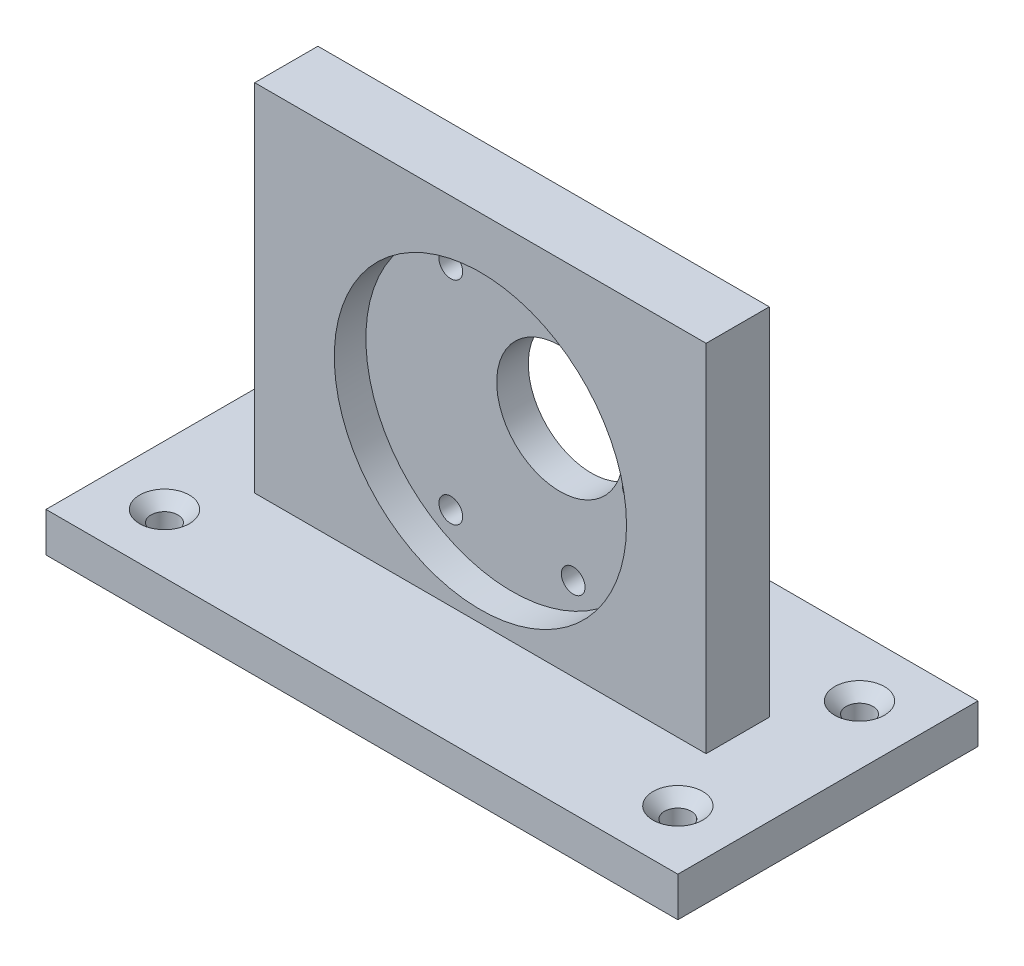
SolidWorks part; units mm, degrees
note: The reader was unsure of these and kept them because the rebuilt part matched: shared geometry of "Sketch3<3>", "Sketch13<2>".
other "Markup1"
sketch "Sketch5" plane through (25, 50, 8) normal (0.9645, 0.1424, 0.2224) x (0.1697, 0.3107, -0.9352)
ref_plane "Front Plane" through (0, 0, 0) normal (0, 0, 1) x (1, 0, 0)
ref_plane "Top Plane" through (0, 0, 0) normal (0, 1, 0) x (1, 0, 0)
ref_plane "Right Plane" through (0, 0, 0) normal (1, 0, 0) x (0, 0, -1)
sketch "Sketch3" plane through (0, 0, 0) normal (0, 0, 1) x (1, 0, 0)
  line L1 (-28.575, 50) -> (28.575, 50)
  line L2 (-28.575, 50) -> (-28.575, 0)
  line L3 (-28.575, 0) -> (28.575, 0)
  line L4 (28.575, 50) -> (28.575, 0)
  line L5 (-7.75, 38.4234) -> (7.75, 38.4234) construction
  line L6 (7.75, 38.4234) -> (15.5, 25) construction
  line L7 (15.5, 25) -> (7.75, 11.5766) construction
  line L8 (7.75, 11.5766) -> (-7.75, 11.5766) construction
  line L9 (-7.75, 11.5766) -> (-15.5, 25) construction
  line L10 (-15.5, 25) -> (-7.75, 38.4234) construction
  line L12 (-20.1843, 13.3466) -> (22.8058, 38.167) construction
  circle A5 centre (-7.75, 38.4234) radius 1.5
  circle A6 centre (7.75, 38.4234) radius 1.5
  circle A8 centre (-7.75, 11.5766) radius 1.5
  circle A9 centre (7.75, 11.5766) radius 1.5
  circle A10 centre (15.5, 25) radius 1.5
  circle A11 centre (6.0622, 28.5) radius 8
  point P4 (0, 0)
  point P27 (-11.625, 18.2883)
  point P28 (11.625, 31.7117)
  dimension "D4" = 25
  dimension "D9" = 16
  dimension "D3" = 3
  dimension "D1" = 50
  dimension "D2" = 57.15
  dimension "D6" = 120
  dimension "D7" = 120
  dimension "D8" = 15.5
  dimension "D10" = 6.4234
extrude "Boss-Extrude1" add sketch "Sketch3" along normal blind 8 contours L2 L3 L4 L1
extrude "Cut-Extrude2" cut sketch "Sketch3<3>" along normal blind 10
sketch "Sketch3<3>" plane through (0, 0, 0) normal (0, 0, 1) x (1, 0, 0) same geometry as "Sketch3"
sketch "Sketch4" plane through (0, 0, 8) normal (0, 0, 1) x (1, 0, 0)
  line L0 (-15.5, 25) -> (15.5, 25) construction
  circle A0 centre (0, 25) radius 18.5
  dimension "D1" = 37
extrude "Cut-Extrude3" cut sketch "Sketch4" against normal blind 4 contours A0
sketch "Sketch6" plane through (0, 0, 8) normal (0, 0, 1) x (1, 0, 0)
  line L1 (-40, 5) -> (40, 5)
  line L2 (-40, 5) -> (-40, 0)
  line L3 (-40, 0) -> (40, 0)
  line L4 (40, 5) -> (40, 0)
  point P4 (0, 0)
  dimension "D1" = 80
  dimension "D2" = 5
extrude "Boss-Extrude2" add sketch "Sketch6" against normal blind 23 and the other way blind 15
sketch "Sketch7" plane through (0, 5, 0) normal (0, 1, 0) x (1, 0, 0)
  line L0 (-40, -23) -> (-40, 15) construction
  line L1 (-40, -23) -> (-32.5, -23)
  line L2 (-40, -23) -> (-40, -15.5)
  line L3 (-40, -15.5) -> (-32.5, -15.5)
  line L4 (-32.5, -23) -> (-32.5, -15.5)
  line L5 (-40, -4) -> (40, -4) construction
  line L6 (40, -23) -> (40, 15) construction
  line L7 (0, 15) -> (0, -23) construction
  line L8 (40, 15) -> (-40, 15) construction
  line L9 (40, -23) -> (-40, -23) construction
  point P18 (-32.5, 7.5)
  point P20 (32.5, -15.5)
  point P21 (32.5, 7.5)
  dimension "D1" = 7.5
hole_wizard "CSK for M3 Flat Head Machine Screw1" positions "Sketch8" profile "Sketch9" countersink size "M3" standard "ANSI Metric" end condition through all
sketch "Sketch8" plane through (0, 5, 0) normal (0, 1, 0) x (1, 0, 0)
  point P0 (-32.5, 7.5)
  point P3 (-32.5, -15.5)
  point P6 (32.5, -15.5)
  point P9 (32.5, 7.5)
sketch "Sketch9" plane through (-32.5, 5, -7.5) normal (1, 0, 0) x (0, 0, 1)
  line L0 (0, 0) -> (0, 5)
  line L1 (0, 5) -> (1.7, 5)
  line L2 (1.7, 5) -> (1.7, 1.45)
  line L3 (1.7, 1.45) -> (3.15, 0)
  line L5 (3.15, 0) -> (0, 0)
  line L6 (-1.7, 1.45) -> (-3.15, 0) construction
  line L11 (0, -6.35) -> (0, 107.95) construction
  dimension "Thru Hole Dia." = 3.4
  dimension "Thru Hole Depth" = 5
  dimension "Near C'Sink Dia." = 6.3
  dimension "Near C'Sink Angle" = 90
sketch "Sketch13" plane through (0, 0, 0) normal (0, 0, -1) x (-1, 0, 0)
  line L0 (20.3378, 28.5) -> (-6.0622, 28.5) construction
  circle A5 centre (20.3378, 28.5) radius 5.08
  circle A7 centre (20.3378, 28.5) radius 6.985
  dimension "D1" = 10.16
  dimension "D2" = 1.905
  dimension "D3" = 26.4
extrude "Boss-Extrude4" add sketch "Sketch13" along normal blind 2.54
extrude "Cut-Extrude6" cut sketch "Sketch16" against normal up to surface (4.826 mm away)
sketch "Sketch16" plane through (-499.2489, 16.8212, -28.3089) normal (0.0361, 0.9993, -0.0009) x (0.0508, -0.0009, 0.9987)
  circle A0 centre (67.5, 464.5) radius 1.7
  circle A2 centre (92.5, 462.5) radius 1.8
  circle A3 centre (113.4, 462.5) radius 1.8
  circle A4 centre (92.5, 401.5) radius 1.8
  circle A5 centre (113.4, 401.5) radius 1.8
  circle A7 centre (67.5, 399.5) radius 1.7
  circle A8 centre (44.5, 399.5) radius 1.7
  circle A9 centre (33.5, 468.8378) radius 1.7
  circle A10 centre (33.5, 435.8378) radius 1.7
  circle A11 centre (44.5, 464.5) radius 1.7
extrude "Cut-Extrude7" cut sketch "Sketch13<2>" against normal blind 3.175
sketch "Sketch13<2>" plane through (0, 0, 0) normal (0, 0, -1) x (-1, 0, 0) same geometry as "Sketch13"
